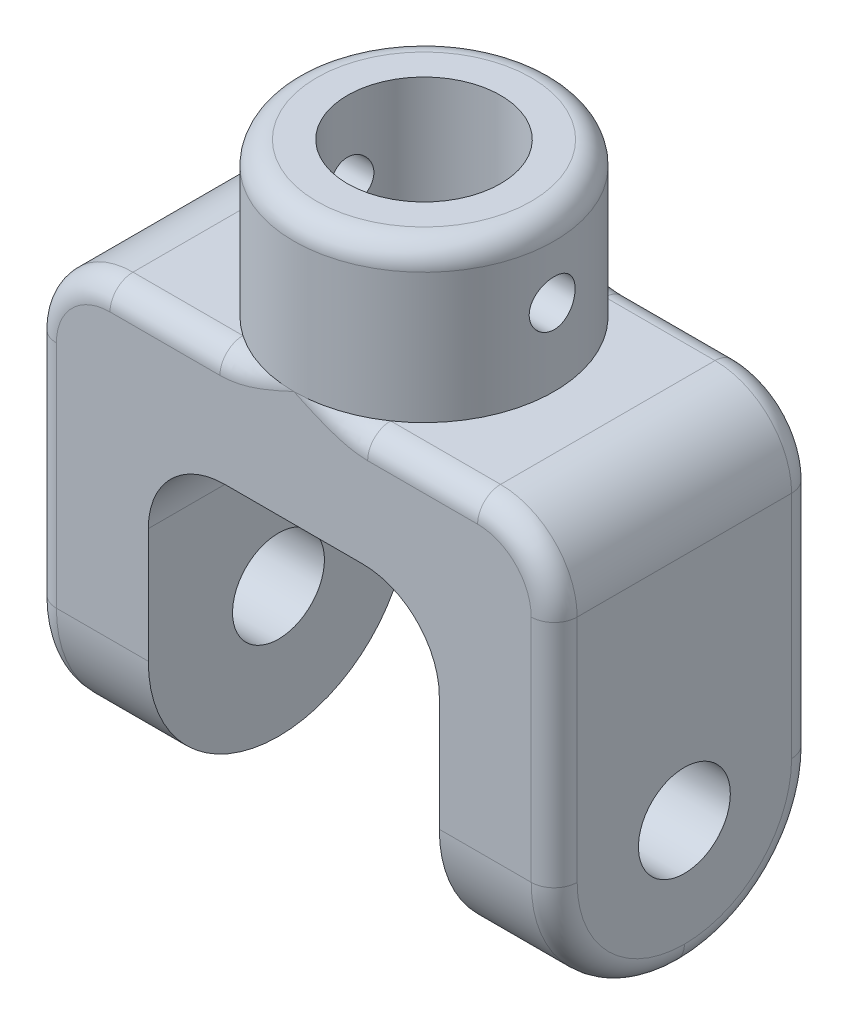
SolidWorks part; units mm, degrees
ref_plane "Front Plane" through (0, 0, 0) normal (0, 0, 1) x (1, 0, 0)
ref_plane "Top Plane" through (0, 0, 0) normal (0, 1, 0) x (1, 0, 0)
ref_plane "Right Plane" through (0, 0, 0) normal (1, 0, 0) x (0, 0, -1)
sketch "Sketch1" plane through (0, 0, 0) normal (0, 0, 1) x (1, 0, 0)
  line L0 (0, 0) -> (0, 85.8519) construction
  line L1 (-34, 57) -> (-34, 0)
  line L2 (-34, 0) -> (-19, 0)
  line L3 (-19, 0) -> (-19, 42)
  line L4 (19, 0) -> (19, 42)
  line L5 (34, 0) -> (19, 0)
  line L6 (34, 57) -> (34, 0)
  line L7 (-19, 42) -> (19, 42)
  line L8 (-34, 57) -> (34, 57)
  dimension "D1" = 57
  dimension "D2" = 38
  dimension "D3" = 15
  dimension "D4" = 15
extrude "Boss-Extrude1" add sketch "Sketch1" along normal mid plane 34
fillet "Fillet1" radius 10 4 edges at (19, 42, 0) (-19, 42, 0) (34, 57, 0) (-34, 57, 0)
sketch "Sketch2" plane through (0, 57, 0) normal (0, 1, 0) x (1, 0, 0)
  circle A0 centre (0, 0) radius 17
  dimension "D1" = 34
extrude "Boss-Extrude2" add sketch "Sketch2" along normal blind 20
hole_wizard "Ø20.0mm Dowel Hole1" positions "Sketch4" profile "Sketch5" hole size "Ø20.0" standard "ANSI Metric" end condition through all
sketch "Sketch4" plane through (0, 77, 0) normal (0, 1, 0) x (1, 0, 0)
  point P0 (0, 0)
sketch "Sketch5" plane through (0, 77, 0) normal (1, 0, 0) x (0, 0, 1)
  line L0 (0, 0) -> (0, 77)
  line L1 (0, 77) -> (10, 77)
  line L2 (10, 77) -> (10, 0)
  line L5 (10, 0) -> (0, 0)
  line L11 (0, -6.35) -> (0, 107.95) construction
  dimension "Thru Hole Dia." = 20
  dimension "Thru Hole Depth" = 77
fillet "Fillet2" radius 17 4 edges at (-26.5, 0, -17) (26.5, 0, -17) (26.5, 0, 17) (-26.5, 0, 17)
hole_wizard "Hole1" positions "Sketch6" profile "Sketch7" legacy end condition through all
sketch "Sketch6" plane through (34, 0, 0) normal (1, 0, 0) x (0, 0, -1)
  point P0 (0, 17)
sketch "Sketch7" plane through (34, 17, 0) normal (0, 1, 0) x (0, 0, -1)
  line L0 (0, 0) -> (0, 68)
  line L1 (0, 68) -> (6, 68)
  line L2 (6, 68) -> (6, 0)
  line L3 (6, 0) -> (0, 0)
  line L4 (0, 110) -> (0, -10) construction
  dimension "Diameter" = 12
  dimension "Depth" = 68
sketch "Sketch8" plane through (0, 0, 0) normal (1, 0, 0) x (0, 0, -1)
  line L0 (17, 77) -> (-17, 77) construction
  circle A0 centre (0, 67) radius 3
  dimension "D1" = 6
  dimension "D2" = 10
extrude "Cut-Extrude1" cut sketch "Sketch8" against normal through all both and the other way through all
fillet "Fillet3" radius 3 17 edges at (0, 77, 17) (-12, 57, 17) (12, 57, 17) (31.0711, 54.0711, 17) (34, 32, 17) (34, 4.9792, 12.0208) (34, 4.9792, -12.0208) (34, 32, -17) (31.0711, 54.0711, -17) (12, 57, -17) (-12, 57, -17) (-31.0711, 54.0711, -17) (-34, 32, -17) (-34, 4.9792, -12.0208) (-34, 4.9792, 12.0208) (-34, 32, 17) (-31.0711, 54.0711, 17)
